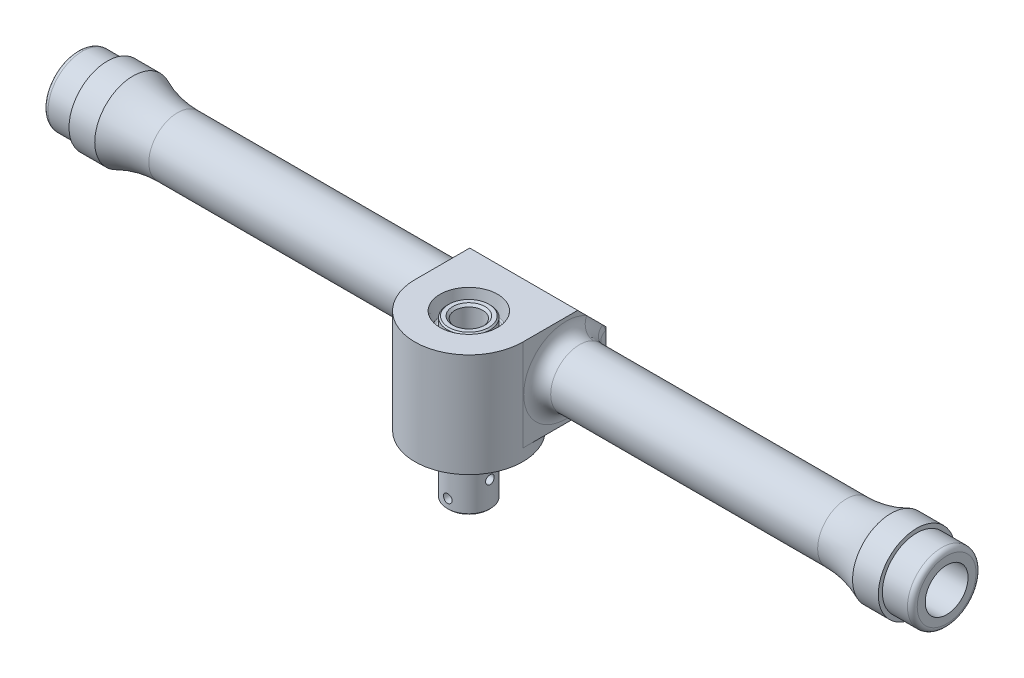
SolidWorks part; units mm, degrees
ref_plane "Płaszczyzna XY" through (0, 0, 0) normal (0, 0, 1) x (1, 0, 0)
ref_plane "Płaszczyzna XZ" through (0, 0, 0) normal (0, 1, 0) x (1, 0, 0)
ref_plane "Płaszczyzna YZ" through (0, 0, 0) normal (1, 0, 0) x (0, 0, -1)
sketch "Szkic1" plane through (0, 0, 0) normal (0, 1, 0) x (1, 0, 0)
  line L1 (20, -25.365) -> (-20, -25.365)
  line L2 (20, -25.365) -> (20, 25.365)
  line L3 (20, 25.365) -> (-20, 25.365)
  line L4 (-20, -25.365) -> (-20, 25.365)
  line L5 (20, -25.365) -> (-20, 25.365) construction
  line L6 (20, 25.365) -> (-20, -25.365) construction
  point P0 (0, 0)
  dimension "D1" = 50.73
  dimension "D2" = 40
extrude "Dodanie-wyciągnięcie1" add sketch "Szkic1" along normal blind 34.04
fillet "Zaokrąglenie2" 2 edges at (20, 17.02, 25.365) (-20, 17.02, 25.365) type full round first side face at (20, 17.02, 0) second side face at (-20, 17.02, 0) middle face at (0, 17.02, 25.365)
sketch "Szkic2" plane through (0, 0, 0) normal (0, -1, 0) x (-1, 0, 0)
  circle A0 centre (0, -5.365) radius 20
extrude "Dodanie-wyciągnięcie2" add sketch "Szkic2" along normal blind 4.39
sketch "Szkic3" plane through (0, -4.39, 0) normal (0, -1, 0) x (-1, 0, 0)
  circle A0 centre (0, -5.365) radius 17.5
extrude "Wytnij-wyciągnięcie1" cut sketch "Szkic3" against normal blind 1.27 contours A0
sketch "Szkic4" plane through (0, 34.04, 0) normal (0, 1, 0) x (1, 0, 0)
  circle A0 centre (0, -5.365) radius 10.67
extrude "Wytnij-wyciągnięcie2" cut sketch "Szkic4" against normal blind 6.6
sketch "Szkic5" plane through (0, -3.12, 0) normal (0, -1, 0) x (-1, 0, 0)
  circle A0 centre (0, -5.365) radius 7.94
extrude "Dodanie-wyciągnięcie4" add sketch "Szkic5" along normal blind 22.86 and the other way blind 35.56 contours A0
sketch "Szkic6" plane through (0, -25.98, 0) normal (0, -1, 0) x (-1, 0, 0)
  circle A0 centre (0, -5.365) radius 5.16
extrude "Wytnij-wyciągnięcie3" cut sketch "Szkic6" against normal up to surface (58.42 mm away) up to face at (0, 32.44, -2.575)
chamfer "Sfazowanie1" distance 10.41 angle 45 2 edges at (0, 0, -25.365) (0, 34.04, -25.365)
sketch "Szkic7" plane through (-20, 0, 0) normal (-1, 0, 0) x (0, 0, 1)
  line L12 (-14.955, 0) -> (5.365, 0) construction
  circle A0 centre (-10.635, 17.02) radius 10.67
  dimension "D1" = 36
  dimension "D2" = 17.02
extrude "Dodanie-wyciągnięcie5" add sketch "Szkic7" along normal blind 120.4 contours A0
sketch "Szkic8" plane through (-140.4, 0, 0) normal (-1, 0, 0) x (0, 0, 1)
  circle A0 centre (-10.635, 17.02) radius 14.225
extrude "Dodanie-wyciągnięcie6" add sketch "Szkic8" along normal blind 9.53
sketch "Szkic9" plane through (-149.93, 0, 0) normal (-1, 0, 0) x (0, 0, 1)
  circle A0 centre (-10.635, 17.02) radius 12.7
  dimension "D1" = 25.4
extrude "Dodanie-wyciągnięcie7" add sketch "Szkic9" along normal blind 11.11 contours A0
fillet "Zaokrąglenie3" radius 40 1 edges at (-140.4, 17.02, 0.035)
fillet "Zaokrąglenie4" radius 5 1 edges at (-20, 17.02, -21.305)
fillet "Zaokrąglenie5" radius 1.8 1 edges at (-161.04, 17.02, 2.065)
mirror "Lustro2" about plane through (0, 0, 0) normal (1, 0, 0) of "Zaokrąglenie5", "Zaokrąglenie4", "Zaokrąglenie3", "Dodanie-wyciągnięcie7", "Dodanie-wyciągnięcie6", "Dodanie-wyciągnięcie5"
sketch "Szkic10" plane through (-161.04, 0, 0) normal (-1, 0, 0) x (0, 0, 1)
  circle A0 centre (-10.635, 17.02) radius 7.94
extrude "Wytnij-wyciągnięcie4" cut sketch "Szkic10" along normal through all and the other way through all
draft "Pochylenie2" type of draft neutral plane draft angle 8 faces to draft 1 face at (0, 27.44, 16.035) neutral plane through (0, 34.04, 0) neutral plane normal (0, 1, 0) parameters "D1"=8
fillet "Zaokrąglenie7" radius 0.5 2 edges at (0, 27.44, 15.1074) (0, 27.44, 13.305)
chamfer "Sfazowanie2" distance 0.81 angle 45 2 edges at (0, -25.98, 0.205) (0, 32.44, 0.205)
chamfer "Sfazowanie3" distance 0.51 angle 45 2 edges at (0, 32.44, -2.575) (0, -25.98, -2.575)
sketch "Szkic11" plane through (0, 0, 0) normal (0, 0, 1) x (1, 0, 0)
  line L0 (-7.43, -25.98) -> (7.43, -25.98) construction
  line L1 (-7.43, -25.98) -> (7.43, -25.98)
  line L2 (0, -25.98) -> (0, -22.17)
  circle A0 centre (0, -22.17) radius 1.59
  dimension "D1" = 3.81
extrude "Wytnij-wyciągnięcie5" cut sketch "Szkic11" against normal through all both and the other way through all contours A0
sketch "Szkic13" plane through (0, 0, 0) normal (1, 0, 0) x (0, 0, -1)
  line L0 (-5.365, -25.98) -> (-5.365, -16.13)
  line L1 (-11.335, -25.98) -> (0.605, -25.98) construction
  circle A0 centre (-5.365, -16.13) radius 1.59
  dimension "D1" = 9.85
extrude "Wytnij-wyciągnięcie6" cut sketch "Szkic13" against normal through all both and the other way through all contours A0
sketch "Szkic14" plane through (0, 0, 0) normal (1, 0, 0) x (0, 0, -1)
  line L0 (-5.365, -25.98) -> (-5.365, 17.02)
  line L1 (-12.795, -25.98) -> (2.065, -25.98) construction
  line L2 (-5.365, 0) -> (-5.365, 34.04) construction
  line L3 (-5.365, 17.02) -> (10.635, 17.02)
  circle A0 centre (10.635, 17.02) radius 7.94 construction
  circle A1 centre (10.635, 17.02) radius 7.94
  dimension "D1" = 43
  dimension "D2" = 16
